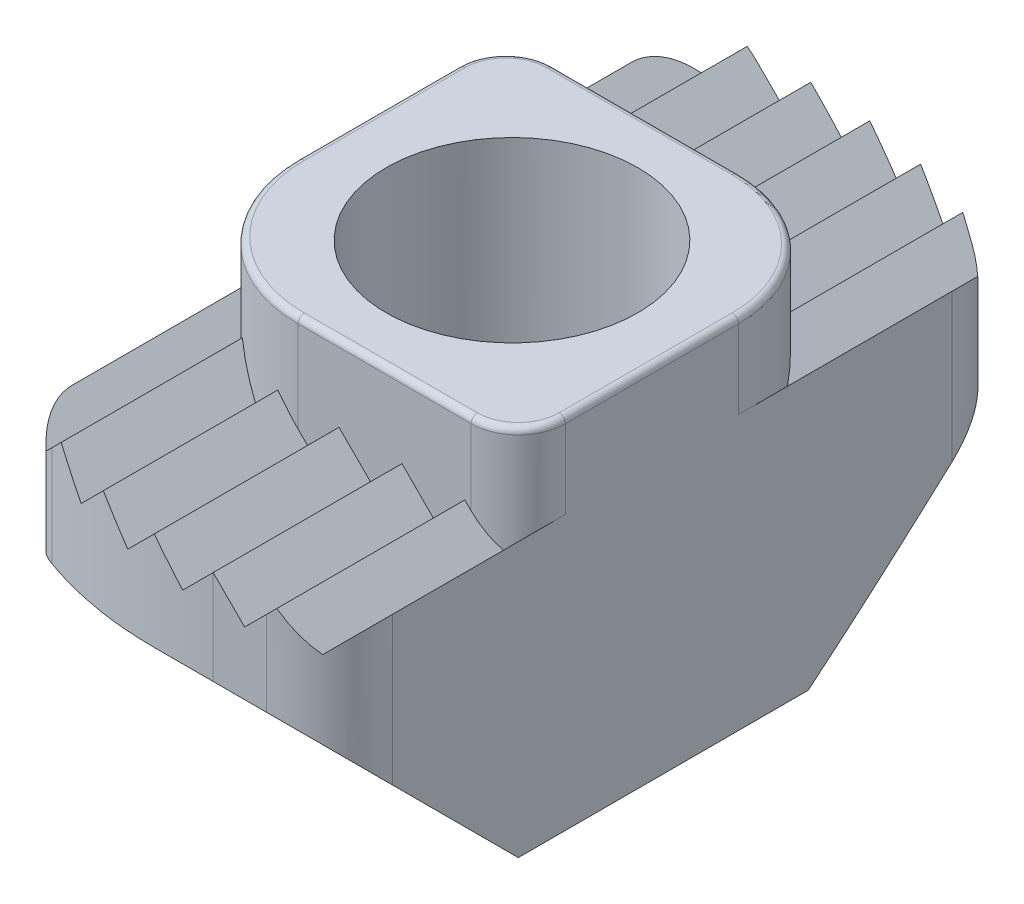
SolidWorks part; units mm, degrees
material "AISI 1020"
ref_plane "Front Plane" through (0, 0, 0) normal (0, 0, 1) x (1, 0, 0)
ref_plane "Top Plane" through (0, 0, 0) normal (0, 1, 0) x (1, 0, 0)
ref_plane "Right Plane" through (0, 0, 0) normal (1, 0, 0) x (0, 0, -1)
sketch "Sketch1" plane through (0, 0, 0) normal (0, 1, 0) x (1, 0, 0)
  line L0 (-1.85, 3.5) -> (-1, 3.5)
  line L1 (2.85, -7) -> (2.85, -1.9468)
  line L2 (1.85, -8) -> (1, -8)
  line L3 (-2.85, 2.5) -> (-2.85, -1.9468)
  line L7 (-2.85, -1.9468) -> (-2.85, -6.3936)
  line L8 (2.85, -1.9468) -> (2.85, 1.8936)
  arc A0 (-2.85, -6.3936) -> (-2.2571, -7.3069) centre (-1.85, -6.3936) ccw
  arc A1 (-2.2571, -7.3069) -> (1, -8) centre (1, 0) ccw
  arc A2 (1.85, -8) -> (2.85, -7) centre (1.85, -7) ccw
  arc A3 (2.85, 1.8936) -> (2.2571, 2.8069) centre (1.85, 1.8936) ccw
  arc A4 (2.2571, 2.8069) -> (-1, 3.5) centre (-1, -4.5) ccw
  arc A5 (-1.85, 3.5) -> (-2.85, 2.5) centre (-1.85, 2.5) ccw
extrude "Extrude1" add sketch "Sketch1" along normal blind 4.5
sketch "Sketch2" plane through (0, 0, 0) normal (0, 0, 1) x (1, 0, 0)
  line L0 (-4, 4.5) -> (-3.5, 4)
  line L1 (-3.5, 4) -> (-3, 4.5)
  line L2 (-3, 4.5) -> (-2.5, 4)
  line L3 (-2.5, 4) -> (-2, 4.5)
  line L4 (-2, 4.5) -> (-1.5, 4)
  line L5 (-1.5, 4) -> (-1, 4.5)
  line L6 (-1, 4.5) -> (-0.5, 4)
  line L7 (-0.5, 4) -> (0, 4.5)
  line L8 (0, 4.5) -> (0.5, 4)
  line L9 (0.5, 4) -> (1, 4.5)
  line L10 (1, 4.5) -> (1.5, 4)
  line L11 (1.5, 4) -> (2, 4.5)
  line L12 (2, 4.5) -> (2.5, 4)
  line L13 (2.5, 4) -> (3, 4.5)
  line L14 (3, 4.5) -> (3.5, 4)
  line L15 (3.5, 4) -> (4, 4.5)
  line L16 (4, 4.5) -> (4, 5.5)
  line L17 (4, 5.5) -> (-4, 5.5)
  line L18 (-4, 5.5) -> (-4, 4.5)
extrude "Cut-Extrude1" cut sketch "Sketch2" against normal blind 8 and the other way blind 8
sketch "Sketch4" plane through (0, 0, 0) normal (1, 0, 0) x (0, 0, -1)
  line L1 (4.5, -1) -> (4.5, 4)
  line L2 (4.5, 4) -> (0.5, 0)
  line L4 (-5, 0) -> (-9, 4)
  line L5 (-9, 4) -> (-9, -1)
  line L6 (-5, 0) -> (0.5, 0)
  line L7 (4.5, -1) -> (-9, -1)
extrude "Cut-Extrude2" cut sketch "Sketch4" against normal blind 4 and the other way blind 4
sketch "Sketch5" plane through (0, 0, 0) normal (1, 0, 0) x (0, 0, -1)
  line L0 (0, -1) -> (-9, -1)
  line L1 (-9, -1) -> (-9, 3)
  line L2 (-9, 3) -> (-8, 3)
  line L3 (-8, 3) -> (-5, 0)
  line L4 (-5, 0) -> (0, 0)
  line L5 (0, 0) -> (0, -1)
  line L6 (0, 3) -> (0, -1) construction
revolve "Cut-Revolve1" cut sketch "Sketch5" angle 60 about L6
sketch "Sketch6" plane through (0, 0, 0) normal (1, 0, 0) x (0, 0, -1)
  line L1 (4.5, -1) -> (4.5, 3)
  line L8 (-4.5, 3) -> (-4.5, -1) construction
  line L10 (-4.5, 0) -> (-4.5, -1)
  line L11 (0.5, 0) -> (-4.5, 0)
  line L12 (3.5, 3) -> (0.5, 0)
  line L13 (4.5, 3) -> (3.5, 3)
  line L14 (-4.5, -1) -> (4.5, -1)
revolve "Cut-Revolve2" cut sketch "Sketch6" angle 60 about L8
sketch "Sketch7" plane through (0, 0, 0) normal (0, -1, 0) x (1, 0, 0)
  line L0 (2.1, 5) -> (-0.65, 5)
  line L2 (-2.1, -0.5) -> (0.85, -0.5)
  line L3 (-2.85, 0.25) -> (-2.85, 2.8)
  line L5 (2.85, 4.25) -> (2.85, 1.5)
  line L6 (2.85, 5) -> (2.85, 0.3918) construction
  arc A0 (2.1, 5) -> (2.85, 4.25) centre (2.1, 4.25) cw
  arc A1 (-0.65, 5) -> (-2.85, 2.8) centre (-0.65, 2.8) ccw
  arc A2 (0.85, -0.5) -> (2.85, 1.5) centre (0.85, 1.5) ccw
  arc A3 (-2.1, -0.5) -> (-2.85, 0.25) centre (-2.1, 0.25) cw
  circle A5 centre (0, 2.25) radius 2
  point P6 (2.85, 5)
  point P17 (-2.85, -0.5)
  point P22 (2.85, 5)
  point P25 (-2.85, -0.5)
  dimension "D1" = 0.75
extrude "Extrude2" add sketch "Sketch7" against normal blind 5.5 from offset 0.2 offset against normal yes
sketch "Sketch10" plane through (0, 5.7, 0) normal (0, 1, 0) x (1, 0, 0)
  circle A0 centre (0, -2.25) radius 2
extrude "Cut-Extrude4" cut sketch "Sketch10" against normal through all
fillet "Fillet1" radius 0.1 8 edges at (-0.625, 5.7, -0.5) (-2.6303, 5.7, -0.2803) (-2.85, 5.7, 1.525) (-2.2056, 5.7, 4.3556) (0.725, 5.7, 5) (2.6303, 5.7, 4.7803) (2.85, 5.7, 2.875) (2.2642, 5.7, 0.0858)
